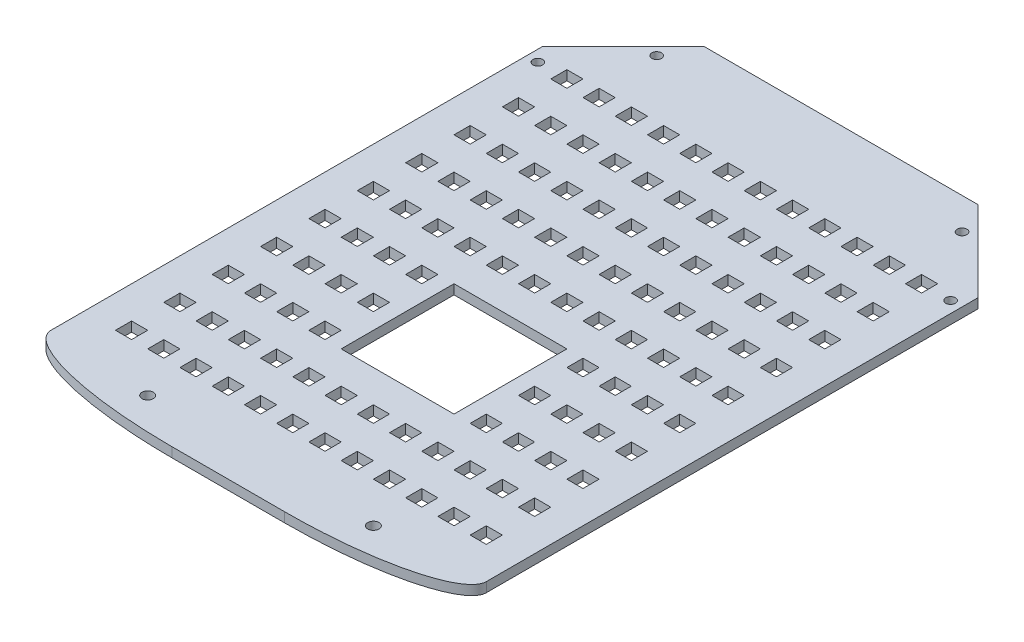
SolidWorks part; units mm, degrees
material "Balsa"
ref_plane "Alzado" through (0, 0, 0) normal (0, 0, 1) x (1, 0, 0)
ref_plane "Planta" through (0, 0, 0) normal (0, 1, 0) x (1, 0, 0)
ref_plane "Vista lateral" through (0, 0, 0) normal (1, 0, 0) x (0, 0, -1)
sketch "Sketch2" plane through (0, 0, 0) normal (0, 1, 0) x (1, 0, 0)
  line L1 (-67.5, 95) -> (67.5, 95)
  line L2 (-67.5, 95) -> (-67.5, -95)
  line L3 (-67.5, -95) -> (67.5, -95)
  line L4 (67.5, 95) -> (67.5, -95)
  line L5 (-67.5, 95) -> (67.5, -95) construction
  line L6 (-67.5, -95) -> (67.5, 95) construction
  point P0 (0, 0)
  dimension "D1" = 135
  dimension "D2" = 190
extrude "Boss-Extrude2" add sketch "Sketch2" along normal blind 3
fillet "Fillet1" radius 12.5 1 edges at (-67.5, 1.5, 95) second distance 50 first distance on face at (-67.5, 1.5, 0)
fillet "Fillet2" radius 12.5 1 edges at (67.5, 1.5, 95) second distance 50 first distance on face at (67.5, 1.5, 0)
sketch "Sketch6" plane through (0, 3, 0) normal (0, 1, 0) x (1, 0, 0)
  line L0 (0, -95) -> (0, 95) construction
  line L1 (-17.5, -95) -> (17.5, -95) construction
  line L2 (67.5, 95) -> (-67.5, 95) construction
  circle A0 centre (35, -85) radius 1.75
  circle A1 centre (-35, -85) radius 1.75
  dimension "D3" = 3.5
  dimension "D1" = 32.5
  dimension "D2" = 2.5
extrude "Cut-Extrude4" cut sketch "Sketch6" against normal blind 10
chamfer "Chamfer4" distance 25 2 edges at (67.5, 1.5, -95) (-67.5, 1.5, -95)
sketch "Sketch12" plane through (0, 3, 0) normal (0, 1, 0) x (1, 0, 0)
  line L0 (0, 95) -> (0, -95) construction
  line L1 (42.5, 95) -> (-42.5, 95) construction
  line L2 (-17.5, -95) -> (17.5, -95) construction
  line L3 (-47.3475, 85.2028) -> (-49.8223, 87.6777) construction
  line L4 (-42.5, 95) -> (-67.5, 70) construction
  line L5 (-49.8223, 87.6777) -> (-67.5, 70) construction
  line L6 (-67.5, 70) -> (-67.5, 65) construction
  line L7 (-67.5, 70) -> (-67.5, -82.5) construction
  line L8 (-64, 65) -> (-67.5, 65) construction
  circle A0 centre (-47.3475, 85.2028) radius 1.5
  circle A1 centre (-64, 65) radius 1.5
  circle A2 centre (64, 65) radius 1.5
  circle A3 centre (47.3475, 85.2028) radius 1.5
  dimension "D5" = 3
  dimension "D1" = 25
  dimension "D2" = 3.5
  dimension "D3" = 3.5
  dimension "D4" = 5
extrude "Cut-Extrude10" cut sketch "Sketch12" against normal blind 10
sketch "Sketch13" plane through (0, 3, 0) normal (0, 1, 0) x (1, 0, 0)
  line L0 (-67.5, 70) -> (-67.5, -82.5) construction
  line L1 (-57.5, -67.5) -> (-52.5, -67.5)
  line L2 (-57.5, -67.5) -> (-57.5, -72.5)
  line L3 (-57.5, -72.5) -> (-52.5, -72.5)
  line L4 (-52.5, -67.5) -> (-52.5, -72.5)
  line L5 (-47.5, -67.5) -> (-47.5, -72.5)
  line L6 (-47.5, -67.5) -> (-42.5, -67.5)
  line L7 (-42.5, -67.5) -> (-42.5, -72.5)
  line L8 (-47.5, -72.5) -> (-42.5, -72.5)
  line L9 (-37.5, -67.5) -> (-37.5, -72.5)
  line L10 (-37.5, -67.5) -> (-32.5, -67.5)
  line L11 (-32.5, -67.5) -> (-32.5, -72.5)
  line L12 (-37.5, -72.5) -> (-32.5, -72.5)
  line L13 (-27.5, -67.5) -> (-27.5, -72.5)
  line L14 (-27.5, -67.5) -> (-22.5, -67.5)
  line L15 (-22.5, -67.5) -> (-22.5, -72.5)
  line L16 (-27.5, -72.5) -> (-22.5, -72.5)
  line L17 (-17.5, -67.5) -> (-17.5, -72.5)
  line L18 (-17.5, -67.5) -> (-12.5, -67.5)
  line L19 (-12.5, -67.5) -> (-12.5, -72.5)
  line L20 (-17.5, -72.5) -> (-12.5, -72.5)
  line L21 (-7.5, -67.5) -> (-7.5, -72.5)
  line L22 (-7.5, -67.5) -> (-2.5, -67.5)
  line L23 (-2.5, -67.5) -> (-2.5, -72.5)
  line L24 (-7.5, -72.5) -> (-2.5, -72.5)
  line L25 (2.5, -67.5) -> (2.5, -72.5)
  line L26 (2.5, -67.5) -> (7.5, -67.5)
  line L27 (7.5, -67.5) -> (7.5, -72.5)
  line L28 (2.5, -72.5) -> (7.5, -72.5)
  line L29 (12.5, -67.5) -> (12.5, -72.5)
  line L30 (12.5, -67.5) -> (17.5, -67.5)
  line L31 (17.5, -67.5) -> (17.5, -72.5)
  line L32 (12.5, -72.5) -> (17.5, -72.5)
  line L33 (22.5, -67.5) -> (22.5, -72.5)
  line L34 (22.5, -67.5) -> (27.5, -67.5)
  line L35 (27.5, -67.5) -> (27.5, -72.5)
  line L36 (22.5, -72.5) -> (27.5, -72.5)
  line L37 (32.5, -67.5) -> (32.5, -72.5)
  line L38 (32.5, -67.5) -> (37.5, -67.5)
  line L39 (37.5, -67.5) -> (37.5, -72.5)
  line L40 (32.5, -72.5) -> (37.5, -72.5)
  line L41 (42.5, -67.5) -> (42.5, -72.5)
  line L42 (42.5, -67.5) -> (47.5, -67.5)
  line L43 (47.5, -67.5) -> (47.5, -72.5)
  line L44 (42.5, -72.5) -> (47.5, -72.5)
  line L45 (52.5, -67.5) -> (52.5, -72.5)
  line L46 (52.5, -67.5) -> (57.5, -67.5)
  line L47 (57.5, -67.5) -> (57.5, -72.5)
  line L48 (52.5, -72.5) -> (57.5, -72.5)
  line L49 (-47.5, -52.5) -> (-47.5, -57.5)
  line L50 (-47.5, -52.5) -> (-42.5, -52.5)
  line L51 (-42.5, -52.5) -> (-42.5, -57.5)
  line L52 (-47.5, -57.5) -> (-42.5, -57.5)
  line L53 (-37.5, -52.5) -> (-37.5, -57.5)
  line L54 (-37.5, -52.5) -> (-32.5, -52.5)
  line L55 (-32.5, -52.5) -> (-32.5, -57.5)
  line L56 (-37.5, -57.5) -> (-32.5, -57.5)
  line L57 (-27.5, -52.5) -> (-27.5, -57.5)
  line L58 (-27.5, -52.5) -> (-22.5, -52.5)
  line L59 (-22.5, -52.5) -> (-22.5, -57.5)
  line L60 (-27.5, -57.5) -> (-22.5, -57.5)
  line L61 (-17.5, -52.5) -> (-17.5, -57.5)
  line L62 (-17.5, -52.5) -> (-12.5, -52.5)
  line L63 (-12.5, -52.5) -> (-12.5, -57.5)
  line L64 (-17.5, -57.5) -> (-12.5, -57.5)
  line L65 (-7.5, -52.5) -> (-7.5, -57.5)
  line L66 (-7.5, -52.5) -> (-2.5, -52.5)
  line L67 (-2.5, -52.5) -> (-2.5, -57.5)
  line L68 (-7.5, -57.5) -> (-2.5, -57.5)
  line L69 (2.5, -52.5) -> (2.5, -57.5)
  line L70 (2.5, -52.5) -> (7.5, -52.5)
  line L71 (7.5, -52.5) -> (7.5, -57.5)
  line L72 (2.5, -57.5) -> (7.5, -57.5)
  line L73 (12.5, -52.5) -> (12.5, -57.5)
  line L74 (12.5, -52.5) -> (17.5, -52.5)
  line L75 (17.5, -52.5) -> (17.5, -57.5)
  line L76 (12.5, -57.5) -> (17.5, -57.5)
  line L77 (22.5, -52.5) -> (22.5, -57.5)
  line L78 (22.5, -52.5) -> (27.5, -52.5)
  line L79 (27.5, -52.5) -> (27.5, -57.5)
  line L80 (22.5, -57.5) -> (27.5, -57.5)
  line L81 (32.5, -52.5) -> (32.5, -57.5)
  line L82 (32.5, -52.5) -> (37.5, -52.5)
  line L83 (37.5, -52.5) -> (37.5, -57.5)
  line L84 (32.5, -57.5) -> (37.5, -57.5)
  line L85 (42.5, -52.5) -> (42.5, -57.5)
  line L86 (42.5, -52.5) -> (47.5, -52.5)
  line L87 (47.5, -52.5) -> (47.5, -57.5)
  line L88 (42.5, -57.5) -> (47.5, -57.5)
  line L89 (52.5, -52.5) -> (52.5, -57.5)
  line L90 (52.5, -52.5) -> (57.5, -52.5)
  line L91 (57.5, -52.5) -> (57.5, -57.5)
  line L92 (52.5, -57.5) -> (57.5, -57.5)
  line L93 (-47.5, -37.5) -> (-47.5, -42.5)
  line L94 (-47.5, -37.5) -> (-42.5, -37.5)
  line L95 (-42.5, -37.5) -> (-42.5, -42.5)
  line L96 (-47.5, -42.5) -> (-42.5, -42.5)
  line L97 (-37.5, -37.5) -> (-37.5, -42.5)
  line L98 (-37.5, -37.5) -> (-32.5, -37.5)
  line L99 (-32.5, -37.5) -> (-32.5, -42.5)
  line L100 (-37.5, -42.5) -> (-32.5, -42.5)
  line L101 (-27.5, -37.5) -> (-27.5, -42.5)
  line L102 (-27.5, -37.5) -> (-22.5, -37.5)
  line L103 (-22.5, -37.5) -> (-22.5, -42.5)
  line L104 (-27.5, -42.5) -> (-22.5, -42.5)
  line L105 (-17.5, -37.5) -> (-17.5, -42.5)
  line L106 (-17.5, -37.5) -> (-12.5, -37.5)
  line L107 (-12.5, -37.5) -> (-12.5, -42.5)
  line L108 (-17.5, -42.5) -> (-12.5, -42.5)
  line L109 (-7.5, -37.5) -> (-7.5, -42.5)
  line L110 (-7.5, -37.5) -> (-2.5, -37.5)
  line L111 (-2.5, -37.5) -> (-2.5, -42.5)
  line L112 (-7.5, -42.5) -> (-2.5, -42.5)
  line L113 (2.5, -37.5) -> (2.5, -42.5)
  line L114 (2.5, -37.5) -> (7.5, -37.5)
  line L115 (7.5, -37.5) -> (7.5, -42.5)
  line L116 (2.5, -42.5) -> (7.5, -42.5)
  line L117 (12.5, -37.5) -> (12.5, -42.5)
  line L118 (12.5, -37.5) -> (17.5, -37.5)
  line L119 (17.5, -37.5) -> (17.5, -42.5)
  line L120 (12.5, -42.5) -> (17.5, -42.5)
  line L121 (22.5, -37.5) -> (22.5, -42.5)
  line L122 (22.5, -37.5) -> (27.5, -37.5)
  line L123 (27.5, -37.5) -> (27.5, -42.5)
  line L124 (22.5, -42.5) -> (27.5, -42.5)
  line L125 (32.5, -37.5) -> (32.5, -42.5)
  line L126 (32.5, -37.5) -> (37.5, -37.5)
  line L127 (37.5, -37.5) -> (37.5, -42.5)
  line L128 (32.5, -42.5) -> (37.5, -42.5)
  line L129 (42.5, -37.5) -> (42.5, -42.5)
  line L130 (42.5, -37.5) -> (47.5, -37.5)
  line L131 (47.5, -37.5) -> (47.5, -42.5)
  line L132 (42.5, -42.5) -> (47.5, -42.5)
  line L133 (52.5, -37.5) -> (52.5, -42.5)
  line L134 (52.5, -37.5) -> (57.5, -37.5)
  line L135 (57.5, -37.5) -> (57.5, -42.5)
  line L136 (52.5, -42.5) -> (57.5, -42.5)
  line L137 (-47.5, -22.5) -> (-47.5, -27.5)
  line L138 (-47.5, -22.5) -> (-42.5, -22.5)
  line L139 (-42.5, -22.5) -> (-42.5, -27.5)
  line L140 (-47.5, -27.5) -> (-42.5, -27.5)
  line L141 (-37.5, -22.5) -> (-37.5, -27.5)
  line L142 (-37.5, -22.5) -> (-32.5, -22.5)
  line L143 (-32.5, -22.5) -> (-32.5, -27.5)
  line L144 (-37.5, -27.5) -> (-32.5, -27.5)
  line L145 (-27.5, -22.5) -> (-27.5, -27.5)
  line L146 (-27.5, -22.5) -> (-22.5, -22.5)
  line L147 (-22.5, -22.5) -> (-22.5, -27.5)
  line L148 (-27.5, -27.5) -> (-22.5, -27.5)
  line L149 (-17.5, -22.5) -> (-17.5, -27.5)
  line L150 (-17.5, -22.5) -> (-12.5, -22.5)
  line L151 (-12.5, -22.5) -> (-12.5, -27.5)
  line L152 (-17.5, -27.5) -> (-12.5, -27.5)
  line L153 (-7.5, -22.5) -> (-7.5, -27.5)
  line L154 (-7.5, -22.5) -> (-2.5, -22.5)
  line L155 (-2.5, -22.5) -> (-2.5, -27.5)
  line L156 (-7.5, -27.5) -> (-2.5, -27.5)
  line L157 (2.5, -22.5) -> (2.5, -27.5)
  line L158 (2.5, -22.5) -> (7.5, -22.5)
  line L159 (7.5, -22.5) -> (7.5, -27.5)
  line L160 (2.5, -27.5) -> (7.5, -27.5)
  line L161 (12.5, -22.5) -> (12.5, -27.5)
  line L162 (12.5, -22.5) -> (17.5, -22.5)
  line L163 (17.5, -22.5) -> (17.5, -27.5)
  line L164 (12.5, -27.5) -> (17.5, -27.5)
  line L165 (22.5, -22.5) -> (22.5, -27.5)
  line L166 (22.5, -22.5) -> (27.5, -22.5)
  line L167 (27.5, -22.5) -> (27.5, -27.5)
  line L168 (22.5, -27.5) -> (27.5, -27.5)
  line L169 (32.5, -22.5) -> (32.5, -27.5)
  line L170 (32.5, -22.5) -> (37.5, -22.5)
  line L171 (37.5, -22.5) -> (37.5, -27.5)
  line L172 (32.5, -27.5) -> (37.5, -27.5)
  line L173 (42.5, -22.5) -> (42.5, -27.5)
  line L174 (42.5, -22.5) -> (47.5, -22.5)
  line L175 (47.5, -22.5) -> (47.5, -27.5)
  line L176 (42.5, -27.5) -> (47.5, -27.5)
  line L177 (52.5, -22.5) -> (52.5, -27.5)
  line L178 (52.5, -22.5) -> (57.5, -22.5)
  line L179 (57.5, -22.5) -> (57.5, -27.5)
  line L180 (52.5, -27.5) -> (57.5, -27.5)
  line L181 (-47.5, -7.5) -> (-47.5, -12.5)
  line L182 (-47.5, -7.5) -> (-42.5, -7.5)
  line L183 (-42.5, -7.5) -> (-42.5, -12.5)
  line L184 (-47.5, -12.5) -> (-42.5, -12.5)
  line L185 (-37.5, -7.5) -> (-37.5, -12.5)
  line L186 (-37.5, -7.5) -> (-32.5, -7.5)
  line L187 (-32.5, -7.5) -> (-32.5, -12.5)
  line L188 (-37.5, -12.5) -> (-32.5, -12.5)
  line L189 (-27.5, -7.5) -> (-27.5, -12.5)
  line L190 (-27.5, -7.5) -> (-22.5, -7.5)
  line L191 (-22.5, -7.5) -> (-22.5, -12.5)
  line L192 (-27.5, -12.5) -> (-22.5, -12.5)
  line L193 (-17.5, -7.5) -> (-17.5, -12.5)
  line L194 (-17.5, -7.5) -> (-12.5, -7.5)
  line L195 (-12.5, -7.5) -> (-12.5, -12.5)
  line L196 (-17.5, -12.5) -> (-12.5, -12.5)
  line L197 (-7.5, -7.5) -> (-7.5, -12.5)
  line L198 (-7.5, -7.5) -> (-2.5, -7.5)
  line L199 (-2.5, -7.5) -> (-2.5, -12.5)
  line L200 (-7.5, -12.5) -> (-2.5, -12.5)
  line L201 (2.5, -7.5) -> (2.5, -12.5)
  line L202 (2.5, -7.5) -> (7.5, -7.5)
  line L203 (7.5, -7.5) -> (7.5, -12.5)
  line L204 (2.5, -12.5) -> (7.5, -12.5)
  line L205 (12.5, -7.5) -> (12.5, -12.5)
  line L206 (12.5, -7.5) -> (17.5, -7.5)
  line L207 (17.5, -7.5) -> (17.5, -12.5)
  line L208 (12.5, -12.5) -> (17.5, -12.5)
  line L209 (22.5, -7.5) -> (22.5, -12.5)
  line L210 (22.5, -7.5) -> (27.5, -7.5)
  line L211 (27.5, -7.5) -> (27.5, -12.5)
  line L212 (22.5, -12.5) -> (27.5, -12.5)
  line L213 (32.5, -7.5) -> (32.5, -12.5)
  line L214 (32.5, -7.5) -> (37.5, -7.5)
  line L215 (37.5, -7.5) -> (37.5, -12.5)
  line L216 (32.5, -12.5) -> (37.5, -12.5)
  line L217 (42.5, -7.5) -> (42.5, -12.5)
  line L218 (42.5, -7.5) -> (47.5, -7.5)
  line L219 (47.5, -7.5) -> (47.5, -12.5)
  line L220 (42.5, -12.5) -> (47.5, -12.5)
  line L221 (52.5, -7.5) -> (52.5, -12.5)
  line L222 (52.5, -7.5) -> (57.5, -7.5)
  line L223 (57.5, -7.5) -> (57.5, -12.5)
  line L224 (52.5, -12.5) -> (57.5, -12.5)
  line L225 (-47.5, 7.5) -> (-47.5, 2.5)
  line L226 (-47.5, 7.5) -> (-42.5, 7.5)
  line L227 (-42.5, 7.5) -> (-42.5, 2.5)
  line L228 (-47.5, 2.5) -> (-42.5, 2.5)
  line L229 (-37.5, 7.5) -> (-37.5, 2.5)
  line L230 (-37.5, 7.5) -> (-32.5, 7.5)
  line L231 (-32.5, 7.5) -> (-32.5, 2.5)
  line L232 (-37.5, 2.5) -> (-32.5, 2.5)
  line L233 (-27.5, 7.5) -> (-27.5, 2.5)
  line L234 (-27.5, 7.5) -> (-22.5, 7.5)
  line L235 (-22.5, 7.5) -> (-22.5, 2.5)
  line L236 (-27.5, 2.5) -> (-22.5, 2.5)
  line L237 (-17.5, 7.5) -> (-17.5, 2.5)
  line L238 (-17.5, 7.5) -> (-12.5, 7.5)
  line L239 (-12.5, 7.5) -> (-12.5, 2.5)
  line L240 (-17.5, 2.5) -> (-12.5, 2.5)
  line L241 (-7.5, 7.5) -> (-7.5, 2.5)
  line L242 (-7.5, 7.5) -> (-2.5, 7.5)
  line L243 (-2.5, 7.5) -> (-2.5, 2.5)
  line L244 (-7.5, 2.5) -> (-2.5, 2.5)
  line L245 (2.5, 7.5) -> (2.5, 2.5)
  line L246 (2.5, 7.5) -> (7.5, 7.5)
  line L247 (7.5, 7.5) -> (7.5, 2.5)
  line L248 (2.5, 2.5) -> (7.5, 2.5)
  line L249 (12.5, 7.5) -> (12.5, 2.5)
  line L250 (12.5, 7.5) -> (17.5, 7.5)
  line L251 (17.5, 7.5) -> (17.5, 2.5)
  line L252 (12.5, 2.5) -> (17.5, 2.5)
  line L253 (22.5, 7.5) -> (22.5, 2.5)
  line L254 (22.5, 7.5) -> (27.5, 7.5)
  line L255 (27.5, 7.5) -> (27.5, 2.5)
  line L256 (22.5, 2.5) -> (27.5, 2.5)
  line L257 (32.5, 7.5) -> (32.5, 2.5)
  line L258 (32.5, 7.5) -> (37.5, 7.5)
  line L259 (37.5, 7.5) -> (37.5, 2.5)
  line L260 (32.5, 2.5) -> (37.5, 2.5)
  line L261 (42.5, 7.5) -> (42.5, 2.5)
  line L262 (42.5, 7.5) -> (47.5, 7.5)
  line L263 (47.5, 7.5) -> (47.5, 2.5)
  line L264 (42.5, 2.5) -> (47.5, 2.5)
  line L265 (52.5, 7.5) -> (52.5, 2.5)
  line L266 (52.5, 7.5) -> (57.5, 7.5)
  line L267 (57.5, 7.5) -> (57.5, 2.5)
  line L268 (52.5, 2.5) -> (57.5, 2.5)
  line L269 (-47.5, 22.5) -> (-47.5, 17.5)
  line L270 (-47.5, 22.5) -> (-42.5, 22.5)
  line L271 (-42.5, 22.5) -> (-42.5, 17.5)
  line L272 (-47.5, 17.5) -> (-42.5, 17.5)
  line L273 (-37.5, 22.5) -> (-37.5, 17.5)
  line L274 (-37.5, 22.5) -> (-32.5, 22.5)
  line L275 (-32.5, 22.5) -> (-32.5, 17.5)
  line L276 (-37.5, 17.5) -> (-32.5, 17.5)
  line L277 (-27.5, 22.5) -> (-27.5, 17.5)
  line L278 (-27.5, 22.5) -> (-22.5, 22.5)
  line L279 (-22.5, 22.5) -> (-22.5, 17.5)
  line L280 (-27.5, 17.5) -> (-22.5, 17.5)
  line L281 (-17.5, 22.5) -> (-17.5, 17.5)
  line L282 (-17.5, 22.5) -> (-12.5, 22.5)
  line L283 (-12.5, 22.5) -> (-12.5, 17.5)
  line L284 (-17.5, 17.5) -> (-12.5, 17.5)
  line L285 (-7.5, 22.5) -> (-7.5, 17.5)
  line L286 (-7.5, 22.5) -> (-2.5, 22.5)
  line L287 (-2.5, 22.5) -> (-2.5, 17.5)
  line L288 (-7.5, 17.5) -> (-2.5, 17.5)
  line L289 (2.5, 22.5) -> (2.5, 17.5)
  line L290 (2.5, 22.5) -> (7.5, 22.5)
  line L291 (7.5, 22.5) -> (7.5, 17.5)
  line L292 (2.5, 17.5) -> (7.5, 17.5)
  line L293 (12.5, 22.5) -> (12.5, 17.5)
  line L294 (12.5, 22.5) -> (17.5, 22.5)
  line L295 (17.5, 22.5) -> (17.5, 17.5)
  line L296 (12.5, 17.5) -> (17.5, 17.5)
  line L297 (22.5, 22.5) -> (22.5, 17.5)
  line L298 (22.5, 22.5) -> (27.5, 22.5)
  line L299 (27.5, 22.5) -> (27.5, 17.5)
  line L300 (22.5, 17.5) -> (27.5, 17.5)
  line L301 (32.5, 22.5) -> (32.5, 17.5)
  line L302 (32.5, 22.5) -> (37.5, 22.5)
  line L303 (37.5, 22.5) -> (37.5, 17.5)
  line L304 (32.5, 17.5) -> (37.5, 17.5)
  line L305 (42.5, 22.5) -> (42.5, 17.5)
  line L306 (42.5, 22.5) -> (47.5, 22.5)
  line L307 (47.5, 22.5) -> (47.5, 17.5)
  line L308 (42.5, 17.5) -> (47.5, 17.5)
  line L309 (52.5, 22.5) -> (52.5, 17.5)
  line L310 (52.5, 22.5) -> (57.5, 22.5)
  line L311 (57.5, 22.5) -> (57.5, 17.5)
  line L312 (52.5, 17.5) -> (57.5, 17.5)
  line L313 (-47.5, 37.5) -> (-47.5, 32.5)
  line L314 (-47.5, 37.5) -> (-42.5, 37.5)
  line L315 (-42.5, 37.5) -> (-42.5, 32.5)
  line L316 (-47.5, 32.5) -> (-42.5, 32.5)
  line L317 (-37.5, 37.5) -> (-37.5, 32.5)
  line L318 (-37.5, 37.5) -> (-32.5, 37.5)
  line L319 (-32.5, 37.5) -> (-32.5, 32.5)
  line L320 (-37.5, 32.5) -> (-32.5, 32.5)
  line L321 (-27.5, 37.5) -> (-27.5, 32.5)
  line L322 (-27.5, 37.5) -> (-22.5, 37.5)
  line L323 (-22.5, 37.5) -> (-22.5, 32.5)
  line L324 (-27.5, 32.5) -> (-22.5, 32.5)
  line L325 (-17.5, 37.5) -> (-17.5, 32.5)
  line L326 (-17.5, 37.5) -> (-12.5, 37.5)
  line L327 (-12.5, 37.5) -> (-12.5, 32.5)
  line L328 (-17.5, 32.5) -> (-12.5, 32.5)
  line L329 (-7.5, 37.5) -> (-7.5, 32.5)
  line L330 (-7.5, 37.5) -> (-2.5, 37.5)
  line L331 (-2.5, 37.5) -> (-2.5, 32.5)
  line L332 (-7.5, 32.5) -> (-2.5, 32.5)
  line L333 (2.5, 37.5) -> (2.5, 32.5)
  line L334 (2.5, 37.5) -> (7.5, 37.5)
  line L335 (7.5, 37.5) -> (7.5, 32.5)
  line L336 (2.5, 32.5) -> (7.5, 32.5)
  line L337 (12.5, 37.5) -> (12.5, 32.5)
  line L338 (12.5, 37.5) -> (17.5, 37.5)
  line L339 (17.5, 37.5) -> (17.5, 32.5)
  line L340 (12.5, 32.5) -> (17.5, 32.5)
  line L341 (22.5, 37.5) -> (22.5, 32.5)
  line L342 (22.5, 37.5) -> (27.5, 37.5)
  line L343 (27.5, 37.5) -> (27.5, 32.5)
  line L344 (22.5, 32.5) -> (27.5, 32.5)
  line L345 (32.5, 37.5) -> (32.5, 32.5)
  line L346 (32.5, 37.5) -> (37.5, 37.5)
  line L347 (37.5, 37.5) -> (37.5, 32.5)
  line L348 (32.5, 32.5) -> (37.5, 32.5)
  line L349 (42.5, 37.5) -> (42.5, 32.5)
  line L350 (42.5, 37.5) -> (47.5, 37.5)
  line L351 (47.5, 37.5) -> (47.5, 32.5)
  line L352 (42.5, 32.5) -> (47.5, 32.5)
  line L353 (52.5, 37.5) -> (52.5, 32.5)
  line L354 (52.5, 37.5) -> (57.5, 37.5)
  line L355 (57.5, 37.5) -> (57.5, 32.5)
  line L356 (52.5, 32.5) -> (57.5, 32.5)
  line L357 (-47.5, 52.5) -> (-47.5, 47.5)
  line L358 (-47.5, 52.5) -> (-42.5, 52.5)
  line L359 (-42.5, 52.5) -> (-42.5, 47.5)
  line L360 (-47.5, 47.5) -> (-42.5, 47.5)
  line L361 (-37.5, 52.5) -> (-37.5, 47.5)
  line L362 (-37.5, 52.5) -> (-32.5, 52.5)
  line L363 (-32.5, 52.5) -> (-32.5, 47.5)
  line L364 (-37.5, 47.5) -> (-32.5, 47.5)
  line L365 (-27.5, 52.5) -> (-27.5, 47.5)
  line L366 (-27.5, 52.5) -> (-22.5, 52.5)
  line L367 (-22.5, 52.5) -> (-22.5, 47.5)
  line L368 (-27.5, 47.5) -> (-22.5, 47.5)
  line L369 (-17.5, 52.5) -> (-17.5, 47.5)
  line L370 (-17.5, 52.5) -> (-12.5, 52.5)
  line L371 (-12.5, 52.5) -> (-12.5, 47.5)
  line L372 (-17.5, 47.5) -> (-12.5, 47.5)
  line L373 (-7.5, 52.5) -> (-7.5, 47.5)
  line L374 (-7.5, 52.5) -> (-2.5, 52.5)
  line L375 (-2.5, 52.5) -> (-2.5, 47.5)
  line L376 (-7.5, 47.5) -> (-2.5, 47.5)
  line L377 (2.5, 52.5) -> (2.5, 47.5)
  line L378 (2.5, 52.5) -> (7.5, 52.5)
  line L379 (7.5, 52.5) -> (7.5, 47.5)
  line L380 (2.5, 47.5) -> (7.5, 47.5)
  line L381 (12.5, 52.5) -> (12.5, 47.5)
  line L382 (12.5, 52.5) -> (17.5, 52.5)
  line L383 (17.5, 52.5) -> (17.5, 47.5)
  line L384 (12.5, 47.5) -> (17.5, 47.5)
  line L385 (22.5, 52.5) -> (22.5, 47.5)
  line L386 (22.5, 52.5) -> (27.5, 52.5)
  line L387 (27.5, 52.5) -> (27.5, 47.5)
  line L388 (22.5, 47.5) -> (27.5, 47.5)
  line L389 (32.5, 52.5) -> (32.5, 47.5)
  line L390 (32.5, 52.5) -> (37.5, 52.5)
  line L391 (37.5, 52.5) -> (37.5, 47.5)
  line L392 (32.5, 47.5) -> (37.5, 47.5)
  line L393 (42.5, 52.5) -> (42.5, 47.5)
  line L394 (42.5, 52.5) -> (47.5, 52.5)
  line L395 (47.5, 52.5) -> (47.5, 47.5)
  line L396 (42.5, 47.5) -> (47.5, 47.5)
  line L397 (52.5, 52.5) -> (52.5, 47.5)
  line L398 (52.5, 52.5) -> (57.5, 52.5)
  line L399 (57.5, 52.5) -> (57.5, 47.5)
  line L400 (52.5, 47.5) -> (57.5, 47.5)
  line L401 (-47.5, 67.5) -> (-47.5, 62.5)
  line L402 (-47.5, 67.5) -> (-42.5, 67.5)
  line L403 (-42.5, 67.5) -> (-42.5, 62.5)
  line L404 (-47.5, 62.5) -> (-42.5, 62.5)
  line L405 (-37.5, 67.5) -> (-37.5, 62.5)
  line L406 (-37.5, 67.5) -> (-32.5, 67.5)
  line L407 (-32.5, 67.5) -> (-32.5, 62.5)
  line L408 (-37.5, 62.5) -> (-32.5, 62.5)
  line L409 (-27.5, 67.5) -> (-27.5, 62.5)
  line L410 (-27.5, 67.5) -> (-22.5, 67.5)
  line L411 (-22.5, 67.5) -> (-22.5, 62.5)
  line L412 (-27.5, 62.5) -> (-22.5, 62.5)
  line L413 (-17.5, 67.5) -> (-17.5, 62.5)
  line L414 (-17.5, 67.5) -> (-12.5, 67.5)
  line L415 (-12.5, 67.5) -> (-12.5, 62.5)
  line L416 (-17.5, 62.5) -> (-12.5, 62.5)
  line L417 (-7.5, 67.5) -> (-7.5, 62.5)
  line L418 (-7.5, 67.5) -> (-2.5, 67.5)
  line L419 (-2.5, 67.5) -> (-2.5, 62.5)
  line L420 (-7.5, 62.5) -> (-2.5, 62.5)
  line L421 (2.5, 67.5) -> (2.5, 62.5)
  line L422 (2.5, 67.5) -> (7.5, 67.5)
  line L423 (7.5, 67.5) -> (7.5, 62.5)
  line L424 (2.5, 62.5) -> (7.5, 62.5)
  line L425 (12.5, 67.5) -> (12.5, 62.5)
  line L426 (12.5, 67.5) -> (17.5, 67.5)
  line L427 (17.5, 67.5) -> (17.5, 62.5)
  line L428 (12.5, 62.5) -> (17.5, 62.5)
  line L429 (22.5, 67.5) -> (22.5, 62.5)
  line L430 (22.5, 67.5) -> (27.5, 67.5)
  line L431 (27.5, 67.5) -> (27.5, 62.5)
  line L432 (22.5, 62.5) -> (27.5, 62.5)
  line L433 (32.5, 67.5) -> (32.5, 62.5)
  line L434 (32.5, 67.5) -> (37.5, 67.5)
  line L435 (37.5, 67.5) -> (37.5, 62.5)
  line L436 (32.5, 62.5) -> (37.5, 62.5)
  line L437 (42.5, 67.5) -> (42.5, 62.5)
  line L438 (42.5, 67.5) -> (47.5, 67.5)
  line L439 (47.5, 67.5) -> (47.5, 62.5)
  line L440 (42.5, 62.5) -> (47.5, 62.5)
  line L441 (52.5, 67.5) -> (52.5, 62.5)
  line L442 (52.5, 67.5) -> (57.5, 67.5)
  line L443 (57.5, 67.5) -> (57.5, 62.5)
  line L444 (52.5, 62.5) -> (57.5, 62.5)
  line L445 (-57.5, -52.5) -> (-57.5, -57.5)
  line L446 (-57.5, -52.5) -> (-52.5, -52.5)
  line L447 (-52.5, -52.5) -> (-52.5, -57.5)
  line L448 (-57.5, -57.5) -> (-52.5, -57.5)
  line L449 (-57.5, -37.5) -> (-57.5, -42.5)
  line L450 (-57.5, -37.5) -> (-52.5, -37.5)
  line L451 (-52.5, -37.5) -> (-52.5, -42.5)
  line L452 (-57.5, -42.5) -> (-52.5, -42.5)
  line L453 (-57.5, -22.5) -> (-57.5, -27.5)
  line L454 (-57.5, -22.5) -> (-52.5, -22.5)
  line L455 (-52.5, -22.5) -> (-52.5, -27.5)
  line L456 (-57.5, -27.5) -> (-52.5, -27.5)
  line L457 (-57.5, -7.5) -> (-57.5, -12.5)
  line L458 (-57.5, -7.5) -> (-52.5, -7.5)
  line L459 (-52.5, -7.5) -> (-52.5, -12.5)
  line L460 (-57.5, -12.5) -> (-52.5, -12.5)
  line L461 (-57.5, 7.5) -> (-57.5, 2.5)
  line L462 (-57.5, 7.5) -> (-52.5, 7.5)
  line L463 (-52.5, 7.5) -> (-52.5, 2.5)
  line L464 (-57.5, 2.5) -> (-52.5, 2.5)
  line L465 (-57.5, 22.5) -> (-57.5, 17.5)
  line L466 (-57.5, 22.5) -> (-52.5, 22.5)
  line L467 (-52.5, 22.5) -> (-52.5, 17.5)
  line L468 (-57.5, 17.5) -> (-52.5, 17.5)
  line L469 (-57.5, 37.5) -> (-57.5, 32.5)
  line L470 (-57.5, 37.5) -> (-52.5, 37.5)
  line L471 (-52.5, 37.5) -> (-52.5, 32.5)
  line L472 (-57.5, 32.5) -> (-52.5, 32.5)
  line L473 (-57.5, 52.5) -> (-57.5, 47.5)
  line L474 (-57.5, 52.5) -> (-52.5, 52.5)
  line L475 (-52.5, 52.5) -> (-52.5, 47.5)
  line L476 (-57.5, 47.5) -> (-52.5, 47.5)
  line L477 (-57.5, 67.5) -> (-57.5, 62.5)
  line L478 (-57.5, 67.5) -> (-52.5, 67.5)
  line L479 (-52.5, 67.5) -> (-52.5, 62.5)
  line L480 (-57.5, 62.5) -> (-52.5, 62.5)
  dimension "D1" = 5
  dimension "D2" = 5
  dimension "D3" = 10
  dimension "D4" = 10
  dimension "D5" = 12
  dimension "D6" = 10
extrude "Cut-Extrude11" cut sketch "Sketch13" against normal through all
sketch "Sketch14" plane through (0, 3, 0) normal (0, 1, 0) x (1, 0, 0)
  line L21 (-17.5, -42.5) -> (17.5, -42.5)
  line L22 (-17.5, -42.5) -> (-17.5, -7.5)
  line L23 (-17.5, -7.5) -> (17.5, -7.5)
  line L24 (17.5, -42.5) -> (17.5, -7.5)
extrude "Cut-Extrude13" cut sketch "Sketch14" against normal through all
